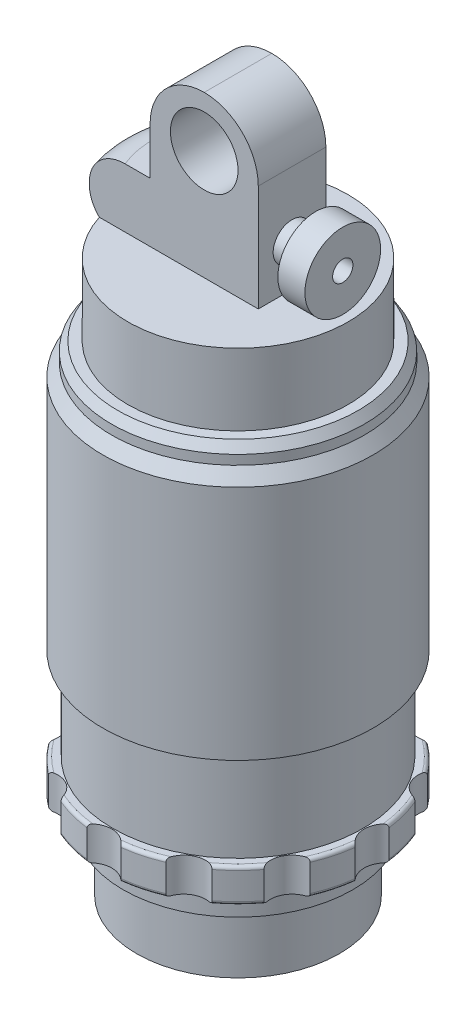
SolidWorks part; units mm, degrees
material "ABS PC"
ref_plane "Front Plane" through (0, 0, 0) normal (0, 0, 1) x (1, 0, 0)
ref_plane "Top Plane" through (0, 0, 0) normal (0, 1, 0) x (1, 0, 0)
ref_plane "Right Plane" through (0, 0, 0) normal (1, 0, 0) x (0, 0, -1)
sketch "Sketch1" plane through (0, 0, 0) normal (0, 1, 0) x (1, 0, 0)
  circle A0 centre (0, 0) radius 12.7
  dimension "D1" = 25.4
extrude "Extrude1" add sketch "Sketch1" along normal blind 103.632
sketch "Sketch12" plane through (0, 0, 0) normal (0, 0, 1) x (1, 0, 0)
  line L0 (0, 0) -> (0, 115.4382) construction
  line L1 (0, 0) -> (-19.05, 0)
  line L2 (-19.05, 0) -> (-19.05, 11.684)
  line L3 (-19.05, 11.684) -> (-21.59, 11.684)
  line L4 (-21.59, 11.684) -> (-21.59, 16.256)
  line L5 (-21.59, 16.256) -> (-25.4, 16.256)
  line L6 (-25.4, 16.256) -> (-25.4, 22.606)
  line L7 (-25.4, 22.606) -> (-23.495, 22.606)
  line L8 (-23.495, 22.606) -> (-23.495, 39.878)
  line L9 (-23.495, 39.878) -> (-25.4, 39.878)
  line L10 (-25.4, 39.878) -> (-25.4, 84.328)
  line L11 (-25.4, 84.328) -> (-23.749, 86.7295)
  line L12 (-23.749, 86.7295) -> (-23.749, 88.5075)
  line L13 (-23.749, 88.5075) -> (-22.606, 90.17)
  line L14 (-22.606, 90.17) -> (-20.701, 90.17)
  line L15 (-20.701, 90.17) -> (-20.701, 103.632)
  line L16 (-20.701, 103.632) -> (0, 103.632)
  line L17 (0, 0) -> (0, 103.632)
  dimension "D1" = 19.05
  dimension "D2" = 43.18
  dimension "D3" = 50.8
  dimension "D4" = 46.99
  dimension "D5" = 50.8
  dimension "D6" = 47.498
  dimension "D7" = 41.402
  dimension "D8" = 45.212
  dimension "D9" = 103.632
  dimension "D10" = 11.684
  dimension "D11" = 16.256
  dimension "D12" = 6.35
  dimension "D13" = 17.272
  dimension "D14" = 44.45
  dimension "D15" = 13.462
  dimension "D16" = 1.778
revolve "Revolve1" add sketch "Sketch12" angle 360 about L0
sketch "Sketch2" plane through (0, 0, 0) normal (0, -1, 0) x (1, 0, 0)
  circle A0 centre (0, 0) radius 12.7
  dimension "D1" = 25.4
extrude "Cut-Extrude1" cut sketch "Sketch2" against normal blind 63.5
sketch "Sketch11" plane through (0, 103.632, 0) normal (0, 1, 0) x (-1, 0, 0)
  circle A0 centre (0, 0) radius 12.7
  dimension "D1" = 25.4
extrude "Extrude6" [suppressed] add sketch "Sketch11" along normal blind 6.35
fillet "Fillet4" [suppressed] radius 5.08
sketch "Sketch3" plane through (0, 103.632, 0) normal (0, 1, 0) x (-1, 0, 0)
  line L0 (-10.16, -6.35) -> (21.59, -6.35)
  line L1 (-10.16, 6.35) -> (21.59, 6.35)
  line L2 (-10.16, 6.35) -> (-10.16, -6.35)
  arc A1 (21.59, 6.35) -> (21.59, -6.35) centre (0, 0) cw
  point P2 (0, 0)
  dimension "D1" = 12.7
  dimension "D2" = 6.35
  dimension "D3" = 10.16
  dimension "D4" = 31.75
extrude "Extrude2" add sketch "Sketch3" along normal blind 11.1125
sketch "Sketch5" plane through (0, 114.7445, 0) normal (0, 1, 0) x (-1, 0, 0)
  line L0 (-10.16, -6.35) -> (21.59, -6.35) construction
  line L1 (-10.16, -6.35) -> (10.16, -6.35)
  line L2 (-10.16, -6.35) -> (-10.16, 6.35)
  line L3 (-10.16, 6.35) -> (10.16, 6.35)
  line L4 (10.16, -6.35) -> (10.16, 6.35)
  line L5 (21.59, 6.35) -> (-10.16, 6.35) construction
  dimension "D1" = 20.32
  dimension "D2" = 10.16
extrude "Extrude3" add sketch "Sketch5" along normal blind 19.05
fillet "Fillet1" radius 10.16 2 edges at (-10.16, 133.7945, 0) (10.16, 133.7945, 0)
sketch "Sketch6" plane through (0, 0, 6.35) normal (0, 0, 1) x (1, 0, 0)
  circle A0 centre (0, 124.2695) radius 6.35
  dimension "D1" = 12.7
  dimension "D2" = 9.525
extrude "Cut-Extrude2" cut sketch "Sketch6" against normal through all
sketch "Sketch13" plane through (0, 0, 0) normal (0, 0, 1) x (1, 0, 0)
  line L0 (3.5886, 111.4298) -> (36.6178, 111.4298) construction
  line L1 (20.701, 103.632) -> (-19.703, 103.632) construction
  line L2 (10.16, 123.6345) -> (10.16, 103.632) construction
  line L3 (10.16, 114.9858) -> (10.16, 111.4298)
  line L4 (10.16, 114.9858) -> (14.605, 114.9858)
  line L5 (14.605, 114.9858) -> (14.605, 118.5418)
  line L6 (14.605, 118.5418) -> (19.685, 118.5418)
  line L7 (19.685, 118.5418) -> (19.685, 113.3348)
  line L8 (19.685, 113.3348) -> (13.335, 113.3348)
  line L9 (13.335, 113.3348) -> (13.335, 111.4298)
  line L10 (13.335, 111.4298) -> (10.16, 111.4298)
  dimension "D1" = 7.7978
  dimension "D2" = 7.112
  dimension "D3" = 14.224
  dimension "D4" = 3.81
  dimension "D5" = 9.525
  dimension "D6" = 5.08
  dimension "D7" = 6.35
revolve "Revolve2" add sketch "Sketch13" angle 360 about L0
sketch "Sketch7" plane through (10.16, 0, 0) normal (1, 0, 0) x (0, 0, -1)
  line L3 (-6.35, 114.7445) -> (6.35, 114.7445) construction
  circle A0 centre (0, 114.7445) radius 8.4667
  dimension "D1" = 16.9333
extrude "Extrude4" [suppressed] add sketch "Sketch7" along normal blind 4.7625
fillet "Fillet2" radius 6.35 2 edges at (-22.5045, 114.7445, 0) (-22.5045, 103.632, 0)
sketch "Sketch9" plane through (0, 0, -6.35) normal (0, 0, -1) x (-1, 0, 0)
  line L0 (21.59, 108.3945) -> (21.59, 108.065) construction
  line L2 (10.16, 114.7445) -> (14.8541, 114.7445) construction
  circle A0 centre (15.24, 109.4105) radius 4.7625
  dimension "D1" = 9.525
  dimension "D2" = 6.35
  dimension "D3" = 5.334
extrude "Extrude5" add sketch "Sketch9" along normal blind 19.05
fillet "Fillet3" radius 2.54 1 edges at (-20.0025, 109.4105, -25.4)
fillet "Fillet5" radius 0.635 3 edges at (0, 16.256, -25.4) (0, 22.606, -25.4) (0, 11.684, -19.05)
sketch "Sketch14" plane through (0, 22.606, 0) normal (0, 1, 0) x (1, 0, 0)
  line L0 (0, 0) -> (-27.7695, 0) construction
  line L1 (0, 0) -> (-24.0491, 13.8847) construction
  line L2 (0, 0) -> (-13.8847, 24.0491) construction
  line L3 (0, 0) -> (0, 27.7695) construction
  line L4 (0, 0) -> (13.8847, 24.0491) construction
  line L5 (0, 0) -> (24.0491, 13.8847) construction
  line L6 (0, 0) -> (27.7695, 0) construction
  line L7 (0, 0) -> (24.0491, -13.8847) construction
  line L8 (0, 0) -> (13.8847, -24.0491) construction
  line L9 (0, 0) -> (0, -27.7695) construction
  line L10 (0, 0) -> (-13.8847, -24.0491) construction
  line L11 (0, 0) -> (-24.0491, -13.8847) construction
  circle A1 centre (0, 0) radius 25.4 construction
  arc A2 (-20.237, 15.35) -> (-23.412, 9.8508) centre (0, 0) ccw
  arc A3 (-25.2008, 3.175) -> (-25.2008, -3.175) centre (0, 0) ccw
  arc A4 (-25.2008, 3.175) -> (-25.2008, -3.175) centre (-27.7695, 0) cw
  arc A5 (-20.237, 15.35) -> (-23.412, 9.8508) centre (-24.0491, 13.8847) cw
  arc A6 (-9.8508, 23.412) -> (-15.35, 20.237) centre (0, 0) ccw
  arc A7 (-9.8508, 23.412) -> (-15.35, 20.237) centre (-13.8847, 24.0491) cw
  arc A8 (3.175, 25.2008) -> (-3.175, 25.2008) centre (0, 0) ccw
  arc A9 (3.175, 25.2008) -> (-3.175, 25.2008) centre (0, 27.7695) cw
  arc A10 (15.35, 20.237) -> (9.8508, 23.412) centre (0, 0) ccw
  arc A11 (15.35, 20.237) -> (9.8508, 23.412) centre (13.8847, 24.0491) cw
  arc A12 (23.412, 9.8508) -> (20.237, 15.35) centre (0, 0) ccw
  arc A13 (23.412, 9.8508) -> (20.237, 15.35) centre (24.0491, 13.8847) cw
  arc A14 (25.2008, -3.175) -> (25.2008, 3.175) centre (0, 0) ccw
  arc A15 (25.2008, -3.175) -> (25.2008, 3.175) centre (27.7695, 0) cw
  arc A16 (20.237, -15.35) -> (23.412, -9.8508) centre (0, 0) ccw
  arc A17 (20.237, -15.35) -> (23.412, -9.8508) centre (24.0491, -13.8847) cw
  arc A18 (9.8508, -23.412) -> (15.35, -20.237) centre (0, 0) ccw
  arc A19 (9.8508, -23.412) -> (15.35, -20.237) centre (13.8847, -24.0491) cw
  arc A20 (-3.175, -25.2008) -> (3.175, -25.2008) centre (0, 0) ccw
  arc A21 (-3.175, -25.2008) -> (3.175, -25.2008) centre (0, -27.7695) cw
  arc A22 (-15.35, -20.237) -> (-9.8508, -23.412) centre (0, 0) ccw
  arc A23 (-15.35, -20.237) -> (-9.8508, -23.412) centre (-13.8847, -24.0491) cw
  arc A24 (-23.412, -9.8508) -> (-20.237, -15.35) centre (0, 0) ccw
  arc A25 (-23.412, -9.8508) -> (-20.237, -15.35) centre (-24.0491, -13.8847) cw
  point P8 (-23.6855, 0)
  point P12 (-20.5122, 11.8428)
  point P17 (-11.8427, 20.5122)
  point P22 (0, 23.6855)
  point P27 (11.8428, 20.5122)
  point P32 (20.5122, 11.8427)
  point P37 (23.6855, 0)
  point P42 (20.5122, -11.8428)
  point P47 (11.8427, -20.5122)
  point P52 (0, -23.6855)
  point P57 (-11.8428, -20.5122)
  point P62 (-20.5122, -11.8427)
  dimension "D1" = 23.6855
  dimension "D2" = 6.35
extrude "Extrude7" cut sketch "Sketch14" against normal up to surface (6.35 mm away) up to face at (0, 16.256, 24.765)
sketch "Sketch15" plane through (0, 0, 0) normal (0, 0, 1) x (1, 0, 0)
  circle A0 centre (0, 124.2695) radius 6.35 construction
  circle A1 centre (0, 124.2695) radius 6.35
